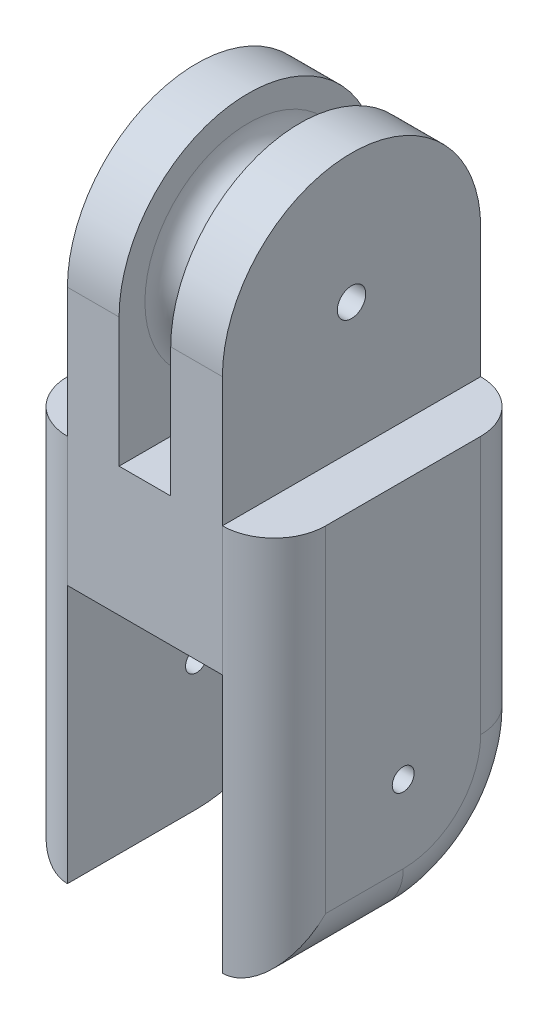
SolidWorks part; units mm, degrees
ref_plane "Front Plane" through (0, 0, 0) normal (0, 0, 1) x (1, 0, 0)
ref_plane "Top Plane" through (0, 0, 0) normal (0, 1, 0) x (1, 0, 0)
ref_plane "Right Plane" through (0, 0, 0) normal (1, 0, 0) x (0, 0, -1)
sketch "Sketch1" plane through (0, 0, 0) normal (0, 1, 0) x (1, 0, 0)
  line L0 (10, 10) -> (-10, -10) construction
  line L1 (-10, 10) -> (10, 10)
  line L2 (-10, 10) -> (-10, -10)
  line L3 (-10, -10) -> (10, -10)
  line L4 (10, 10) -> (10, -10)
  line L5 (-10, 10) -> (10, -10) construction
  point P5 (0, 0)
  dimension "D1" = 20
  dimension "D2" = 20
extrude "Boss-Extrude1" add sketch "Sketch1" along normal blind 10
sketch "Sketch4" plane through (0, 0, 0) normal (0, -1, 0) x (1, 0, 0)
  line L0 (10, -10) -> (-10, -10) construction
  line L1 (-10, 10) -> (-6, 10)
  line L2 (-10, 10) -> (-10, -10)
  line L3 (-10, -10) -> (-6, -10)
  line L4 (-6, 10) -> (-6, -10)
  line L5 (-10, 10) -> (10, 10) construction
  line L6 (10, -10) -> (6, -10)
  line L7 (10, -10) -> (10, 10)
  line L8 (10, 10) -> (6, 10)
  line L9 (6, -10) -> (6, 10)
  dimension "D1" = 4
  dimension "D2" = 4
extrude "Boss-Extrude2" add sketch "Sketch4" along normal blind 10
sketch "Sketch5" plane through (-10, 0, 0) normal (-1, 0, 0) x (0, 0, 1)
  line L0 (10, -10) -> (-10, -10) construction
  line L4 (0, -20) -> (10, -20)
  line L5 (10, -10) -> (10, -20)
  arc A0 (10, -10) -> (0, -20) centre (0, -10) ccw
extrude "Boss-Extrude3" add sketch "Sketch5" against normal blind 4
sketch "Sketch6" plane through (10, 0, 0) normal (1, 0, 0) x (0, 0, -1)
  line L0 (10, -10) -> (-10, -10) construction
  line L4 (0, -20) -> (-10, -20)
  line L5 (-10, -10) -> (-10, -20)
  arc A0 (0, -20) -> (-10, -10) centre (0, -10) ccw
extrude "Boss-Extrude4" add sketch "Sketch6" against normal blind 4
sketch "Sketch7" plane through (-10, 0, 0) normal (-1, 0, 0) x (0, 0, 1)
  circle A0 centre (0, -10) radius 0.85
  dimension "D1" = 1.7
extrude "Cut-Extrude1" cut sketch "Sketch7" against normal through all
fillet "Fillet1" radius 4 8 edges at (-10, -5, 10) (-10, -17.0711, -7.0711) (10, -5, 10) (10, -17.0711, -7.0711) (-10, 0, -10) (10, 0, -10) (10, -20, 5) (-10, -20, 5)
sketch "Sketch8" plane through (0, 10, 0) normal (0, 1, 0) x (1, 0, 0)
  line L0 (6, 10) -> (-6, 10) construction
  line L1 (6, -10) -> (2, -10)
  line L2 (6, -10) -> (6, 10)
  line L3 (6, 10) -> (2, 10)
  line L4 (2, -10) -> (2, 10)
  line L5 (-10, 6) -> (-10, -6) construction
  line L6 (-6, -10) -> (-2, -10)
  line L7 (-6, -10) -> (-6, 10)
  line L8 (-6, 10) -> (-2, 10)
  line L9 (-2, -10) -> (-2, 10)
  line L10 (10, -6) -> (10, 6) construction
  dimension "D1" = 4
  dimension "D2" = 4
  dimension "D3" = 4
  dimension "D4" = 4
extrude "Boss-Extrude5" add sketch "Sketch8" along normal blind 10
sketch "Sketch9" plane through (6, 0, 0) normal (1, 0, 0) x (0, 0, -1)
  line L0 (-10, 20) -> (10, 20) construction
  circle A0 centre (0, 20) radius 10
extrude "Boss-Extrude6" add sketch "Sketch9" against normal blind 4
sketch "Sketch10" plane through (-6, 0, 0) normal (-1, 0, 0) x (0, 0, 1)
  line L0 (-10, 20) -> (10, 20) construction
  circle A0 centre (0, 20) radius 10
extrude "Boss-Extrude7" add sketch "Sketch10" against normal blind 4
sketch "Sketch12" plane through (-6, 0, 0) normal (-1, 0, 0) x (0, 0, 1)
  circle A0 centre (0, 20) radius 1.1
  dimension "D1" = 2.2
extrude "Cut-Extrude2" cut sketch "Sketch12" against normal through all
sketch "Sketch13" plane through (-2, 0, 0) normal (1, 0, 0) x (0, 0, -1)
  circle A0 centre (0, 20) radius 6
  dimension "D1" = 12
sketch "Sketch14" plane through (-2, 0, 0) normal (1, 0, 0) x (0, 0, -1)
  circle A0 centre (0, 20) radius 1.1
  dimension "D1" = 2.2
extrude "Boss-Extrude8" add sketch "Sketch13" along normal blind 4
extrude "Cut-Extrude3" cut sketch "Sketch14" along normal blind 4
fillet "Fillet2" radius 2 2 edges at (2, 20, -6) (-2, 20, 6)
sketch "Sketch16" plane through (0, 0, 0) normal (0, -1, 0) x (1, 0, 0)
  line L0 (6, -10) -> (-6, -10) construction
  line L1 (-6, 0) -> (6, 0) construction
  line L2 (-6, -10) -> (-6, 10) construction
  line L3 (6, 10) -> (6, -10) construction
  circle A0 centre (0, -6) radius 0.5
  circle A1 centre (0, 6) radius 0.5
  dimension "D1" = 1
  dimension "D2" = 4
extrude "Cut-Extrude4" cut sketch "Sketch16" against normal up to next
